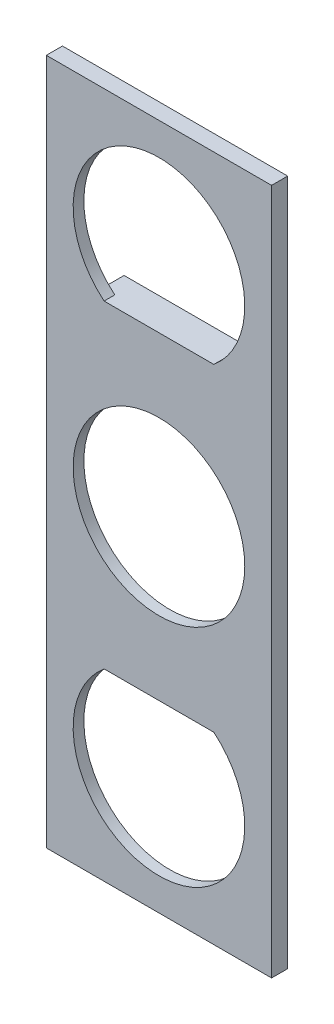
SolidWorks part; units mm, degrees
material "ABS PC"
ref_plane "Front Plane" through (0, 0, 0) normal (0, 0, 1) x (1, 0, 0)
ref_plane "Top Plane" through (0, 0, 0) normal (0, 1, 0) x (1, 0, 0)
ref_plane "Right Plane" through (0, 0, 0) normal (1, 0, 0) x (0, 0, -1)
sketch "Sketch1" plane through (0, 0, 0) normal (0, 0, 1) x (1, 0, 0)
  line L0 (12.5, -24.6985) -> (12.5, -29.6985)
  line L9 (-12.5, 29.6985) -> (12.5, 29.6985)
  line L10 (-12.5, 29.6985) -> (-12.5, 24.6985)
  line L11 (-12.5, 24.6985) -> (12.5, 24.6985)
  line L12 (12.5, 29.6985) -> (12.5, 24.6985)
  line L13 (-12.5, -29.6985) -> (12.5, -29.6985)
  line L14 (-12.5, -24.6985) -> (-12.5, -29.6985)
  line L15 (-12.5, -24.6985) -> (12.5, -24.6985)
extrude "Boss-Extrude1" add sketch "Sketch1" along normal blind 6
sketch "Sketch2" plane through (0, 0, 6) normal (0, 0, 1) x (1, 0, 0)
  line L1 (-21, 64) -> (21, 64)
  line L2 (-21, 64) -> (-21, -64)
  line L3 (-21, -64) -> (21, -64)
  line L4 (21, 64) -> (21, -64)
  line L5 (17, 60) -> (17, -60)
  line L6 (-17, -60) -> (17, -60)
  line L7 (-17, 60) -> (-17, -60)
  line L8 (-17, 60) -> (17, 60)
  circle A0 centre (0, 0) radius 16
  circle A1 centre (0, -42) radius 16
  circle A2 centre (0, 42) radius 16
  line M12 (12.5, -24.6985) -> (-12.5, -24.6985)
  line M13 (-12.5, -24.6985) -> (-12.5, -29.6985)
  line M14 (-12.5, -29.6985) -> (12.5, -29.6985)
  line M15 (12.5, -29.6985) -> (12.5, -24.6985)
  dimension "D1" = 2
  dimension "D3" = 4
  dimension "D2" = 2
extrude "Boss-Extrude2" add sketch "Sketch2" against normal blind 3 separate body contours L4 L1 L2 L3 L7 L8 L5 L6 region at (0, 62.6529, 6)
extrude "Boss-Extrude3" add sketch "Sketch2<3>" against normal blind 2 contours L8 L7 L6 L5 A2 A1 A0 M14 M13 M12 M15 region at (16.8753, 0, 6)
sketch "Sketch2<3>" plane through (0, 0, 6) normal (0, 0, 1) x (1, 0, 0) same geometry as "Sketch2"
